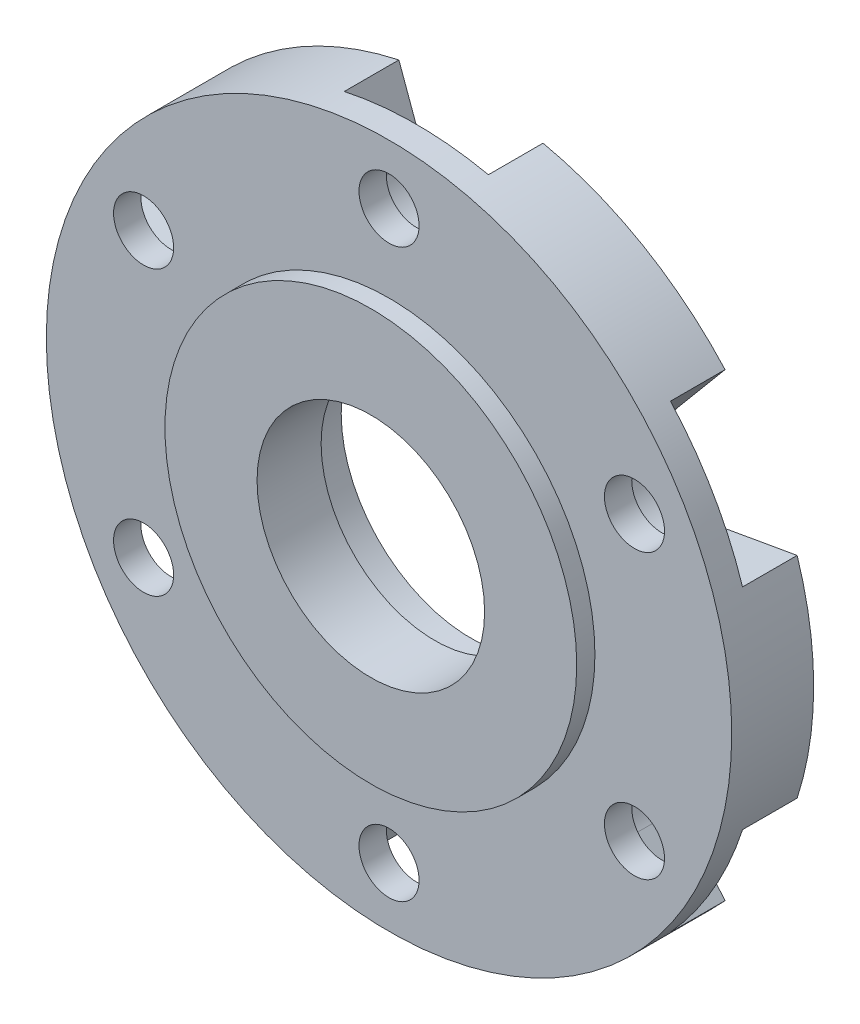
SolidWorks part; units mm, degrees
material "6061-T6 (SS)"
ref_plane "Front Plane" through (0, 0, 0) normal (0, 0, 1) x (1, 0, 0)
ref_plane "Top Plane" through (0, 0, 0) normal (0, 1, 0) x (1, 0, 0)
ref_plane "Right Plane" through (0, 0, 0) normal (1, 0, 0) x (0, 0, -1)
sketch "Sketch Spindle Skeleton" plane through (0, 0, 0) normal (1, 0, 0) x (0, 0, -1)
  line L0 (-95.847, -9.525) -> (-141.966, -9.525)
  line L5 (-1000, 0) -> (49000, 0)
  line L6 (0, -9.525) -> (0, 9.525)
  line L13 (0, 9.525) -> (-45.847, 9.525)
  line L26 (-45.847, 9.525) -> (-45.847, 12.7)
  line L27 (-45.847, 12.7) -> (-95.847, 12.7)
  line L32 (-95.847, 12.7) -> (-95.847, 9.525)
  line L34 (-160, 7) -> (-160, -7)
  line L36 (-95.847, -9.525) -> (-95.847, -12.7)
  line L37 (-95.847, -12.7) -> (-45.847, -12.7)
  line L38 (-45.847, -12.7) -> (-45.847, -9.525)
  line L39 (0, -9.525) -> (-45.847, -9.525)
  line L40 (-25.305, 37.6491) -> (-16.305, 37.6491)
  line L41 (-111.341, 22.6187) -> (-95.847, 22.6187)
  line L42 (-111.341, 22.6187) -> (-111.341, -22.6187)
  line L43 (-111.341, -22.6187) -> (-95.847, -22.6187)
  line L44 (-95.847, 22.6187) -> (-95.847, -22.6187)
  line L45 (-111.341, 22.6187) -> (-95.847, -22.6187) construction
  line L46 (-111.341, -22.6187) -> (-95.847, 22.6187) construction
  line L47 (-30.353, 22.6187) -> (-45.847, 22.6187)
  line L48 (-30.353, 22.6187) -> (-30.353, -22.6187)
  line L49 (-30.353, -22.6187) -> (-45.847, -22.6187)
  line L50 (-45.847, 22.6187) -> (-45.847, -22.6187)
  line L51 (-30.353, 22.6187) -> (-45.847, -22.6187) construction
  line L52 (-30.353, -22.6187) -> (-45.847, 22.6187) construction
  line L59 (-16.305, 37.6491) -> (-16.305, -37.6491)
  line L60 (-16.305, -37.6491) -> (-25.305, -37.6491)
  line L61 (-25.305, -22.6187) -> (-27.305, -22.6187)
  line L62 (-27.305, -22.6187) -> (-27.305, -12.5)
  line L63 (-27.305, -12.5) -> (-25.305, -12.5)
  line L64 (-25.305, -12.5) -> (-25.305, 12.5)
  line L65 (-25.305, 12.5) -> (-27.305, 12.5)
  line L66 (-27.305, 12.5) -> (-27.305, 22.6187)
  line L67 (-27.305, 22.6187) -> (-25.305, 22.6187)
  line L68 (-25.305, 22.6187) -> (-25.305, 37.6491)
  line L69 (-25.305, -22.6187) -> (-25.305, -37.6491)
  line L71 (-119.469, 37.6491) -> (-26.305, 37.6491)
  line L72 (-119.469, 37.6491) -> (-119.469, -37.6491)
  line L73 (-119.469, -37.6491) -> (-26.305, -37.6491)
  line L74 (-26.305, 37.6491) -> (-26.305, -37.6491)
  line L75 (-119.469, 37.6491) -> (-26.305, -37.6491) construction
  line L76 (-119.469, -37.6491) -> (-26.305, 37.6491) construction
  line L78 (-147.3, -7) -> (-160, -7)
  line L79 (-95.847, 9.525) -> (-141.966, 9.525)
  line L80 (-147.3, 7) -> (-160, 7)
  line L82 (-118.9065, 9.525) -> (-118.9065, -9.525) construction
  line L83 (-22.9235, 9.525) -> (-22.9235, -9.525) construction
  line L96 (-119.469, 37.6492) -> (-134.709, 37.6492)
  line L98 (-119.469, -37.6491) -> (-134.709, -37.6491)
  line L99 (-134.709, 37.6492) -> (-134.709, -37.6491)
  line L110 (-119.469, 37.6492) -> (-119.469, -37.6491)
  line L111 (-147.3, 7) -> (-147.3, 7.493)
  line L112 (-147.3, 7.493) -> (-141.966, 7.493)
  line L113 (-141.966, 7.493) -> (-141.966, 9.525)
  line L114 (-141.966, -9.525) -> (-141.966, -7.493)
  line L115 (-141.966, -7.493) -> (-147.3, -7.493)
  line L116 (-147.3, -7.493) -> (-147.3, -7)
  point P3 (0, 0)
  point P18 (-103.594, 0)
  point P24 (-38.1, 0)
  point P29 (-72.887, 0)
  point P48 (-16.305, 31.1339)
  point P70 (-134.709, 31.1339)
revolve "Main Revolve" add sketch "Sketch Spindle Skeleton" angle 360 about L5 region at (0, 23.3554, 20.9972) region at (0, 17.5594, 26.805)
sketch "Sketch Center Cut" plane through (0, 0, 25.305) normal (0, 0, 1) x (1, 0, 0)
  circle A3 centre (0, 0) radius 12.5
  dimension "D1" = 25
extrude "Cut Center" cut sketch "Sketch Center Cut" against normal through all both and the other way through all
hole_wizard "CBORE for M6 SHCS1" positions "Hole wizard sketch 1" profile "Hole wizard sketch 2" counterbore size "M6" standard "ANSI Metric" end condition through all
sketch "Hole wizard sketch 1" plane through (0, 0, 16.305) normal (0, 0, -1) x (-1, 0, 0)
  point P0 (0, 31.1339)
sketch "Hole wizard sketch 2" plane through (0, 31.1339, 16.305) normal (1, 0, 0) x (0, 1, 0)
  line L0 (0, 0) -> (0, 11)
  line L1 (0, 11) -> (3.3, 11)
  line L3 (3.3, 11) -> (3.3, 6)
  line L4 (3.3, 6) -> (5.5, 6)
  line L5 (5.5, 6) -> (5.5, 0)
  line L7 (5.5, 0) -> (0, 0)
  line L11 (0, -6.35) -> (0, 107.95) construction
  dimension "Thru Hole Dia." = 6.6
  dimension "Thru Hole Depth" = 11
  dimension "C'Bore Dia." = 11
  dimension "C'Bore Depth" = 6
pattern_circular "CirPattern1" count 6 over 360 about axis through (0, 0, 16.305) along (0, 0, 1) of "CBORE for M6 SHCS1"
sketch "Sketch1" plane through (0, 0, 16.305) normal (0, 0, -1) x (-1, 0, 0)
  circle A0 centre (0, 0) radius 14.2558
  dimension "D1" = 28.5115
extrude "Cut-Extrude1" cut sketch "Sketch1" against normal blind 3.9624
sketch "Sketch2" plane through (0, 0, 16.305) normal (0, 0, -1) x (-1, 0, 0)
  line L0 (-5.1683, 29.2528) -> (-7.9179, 36.8071)
  line L1 (0, 31.1339) -> (0, 37.65) construction
  line L2 (5.1683, 29.2528) -> (7.9179, 36.8071)
  circle A0 centre (0, 31.1339) radius 5.5 construction
  circle A1 centre (0, 0) radius 37.6491 construction
  arc A2 (-5.1683, 29.2528) -> (5.1683, 29.2528) centre (0, 31.1339) ccw
  point P37 (0.065, 0.0375)
  circle M8 centre (0, 31.1339) radius 5.5
  circle M9 centre (0, 0) radius 37.6491
  dimension "D1" = 20
extrude "Cut-Extrude2" cut sketch "Sketch2" against normal up to surface (6 mm away) contours L1 L2 M8 M9 | L1 L0 M8 M9 region at (4.7304, 35.5149, 16.305) region at (-4.7304, 35.5149, 16.305) up to face at (23.6628, -15.567, 22.305)
pattern_circular "CirPattern2" count 6 over 360 about axis through (0, 0, 1000) along (0, 0, 1) of "Cut-Extrude2" reverse direction yes
